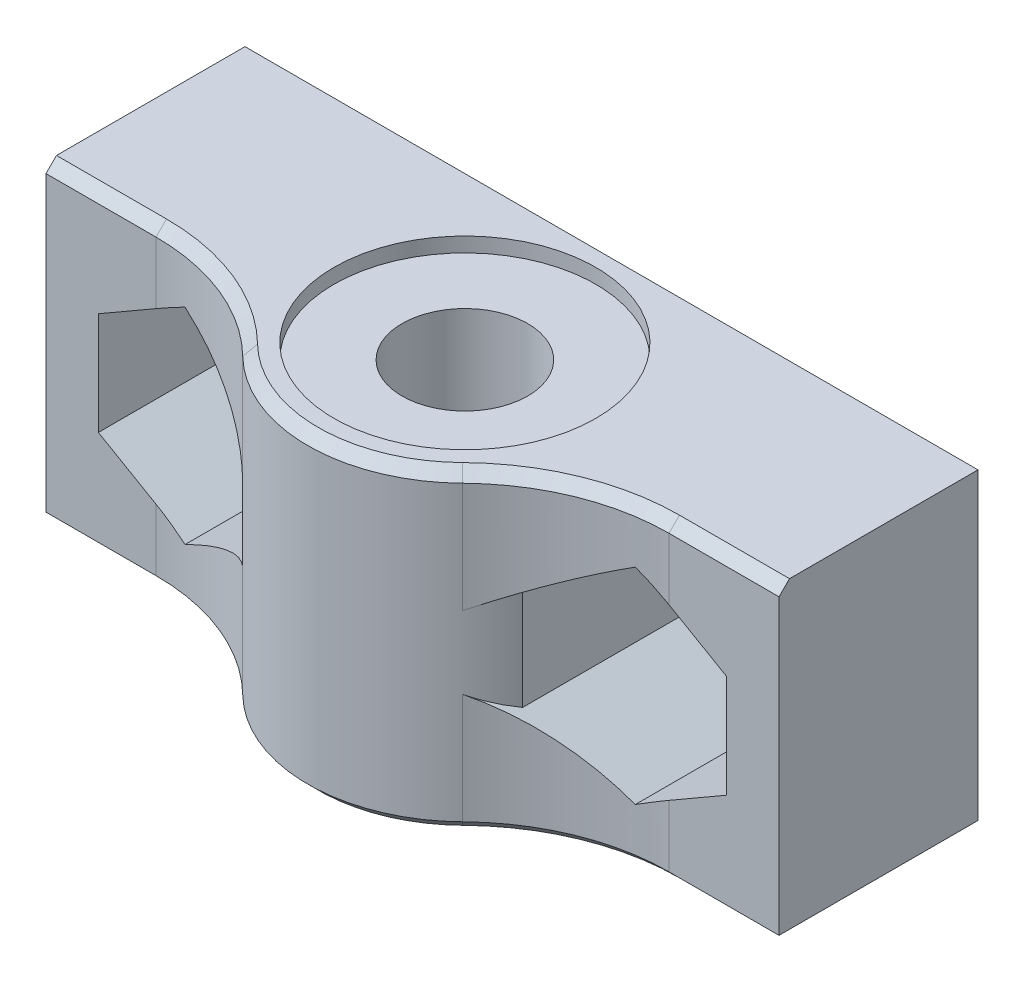
SolidWorks part; units mm, degrees
note: The reader was unsure of these and kept them because the rebuilt part matched: shared geometry of "Sketch6<3>".
ref_plane "Front Plane" through (0, 0, 0) normal (0, 0, 1) x (1, 0, 0)
ref_plane "Top Plane" through (0, 0, 0) normal (0, 1, 0) x (1, 0, 0)
ref_plane "Right Plane" through (0, 0, 0) normal (1, 0, 0) x (0, 0, -1)
sketch "Sketch1" plane through (0, 0, 0) normal (0, 0, 1) x (1, 0, 0)
  line L1 (-17.5, 0) -> (17.5, 0)
  line L2 (-17.5, 0) -> (-17.5, -15)
  line L3 (-17.5, -15) -> (17.5, -15)
  line L4 (17.5, 0) -> (17.5, -15)
  point P4 (0, 0)
  dimension "D1" = 35
  dimension "D2" = 15
extrude "Boss-Extrude1" add sketch "Sketch1" along normal blind 10
sketch "Sketch3" plane through (0, 0, 0) normal (0, 1, 0) x (1, 0, 0)
  line L0 (17.5, 0) -> (-17.5, 0) construction
  line L1 (0, -10) -> (0, -7.5) construction
  line L3 (17.5, -10) -> (-17.5, -10) construction
  circle A0 centre (0, -7.5) radius 7.5
  dimension "D1" = 15
extrude "Boss-Extrude2" add sketch "Sketch3" against normal through all
sketch "Sketch2" plane through (0, 0, 10) normal (0, 0, 1) x (1, 0, 0)
  line L0 (-17.5, -7.5) -> (-10.75, -7.5) construction
  line L1 (-10.75, -12.4075) -> (-6.5, -9.9537)
  line L2 (-6.5, -9.9537) -> (-6.5, -5.0463)
  line L3 (-6.5, -5.0463) -> (-10.75, -2.5925)
  line L4 (-10.75, -2.5925) -> (-15, -5.0463)
  line L5 (-15, -5.0463) -> (-15, -9.9537)
  line L6 (-15, -9.9537) -> (-10.75, -12.4075)
  line L7 (-17.5, 0) -> (-17.5, -15) construction
  line L8 (-10.75, -2.5925) -> (-10.75, -7.5) construction
  circle A0 centre (-10.75, -7.5) radius 4.25 construction
  dimension "D1" = 8.5
  dimension "D2" = 2.5
extrude "Cut-Extrude1" cut sketch "Sketch2" against normal blind 7.5 and the other way blind 10
sketch "Sketch5" plane through (0, 0, 2.5) normal (0, 0, 1) x (1, 0, 0)
  line L0 (-10.75, -2.5925) -> (-10.75, -12.4075) construction
  circle A0 centre (-10.75, -7.5) radius 2.75
  dimension "D1" = 5.5
extrude "Cut-Extrude3" cut sketch "Sketch5" against normal through all
mirror "Mirror1" about plane through (0, 0, 0) normal (1, 0, 0) of "Cut-Extrude3", "Cut-Extrude1"
sketch "Sketch4" plane through (0, 0, 0) normal (0, 1, 0) x (1, 0, 0)
  circle A0 centre (0, -7.5) radius 3
  arc A1 (-7.0711, -10) -> (7.0711, -10) centre (0, -7.5) ccw construction
  dimension "D1" = 6
extrude "Cut-Extrude2" cut sketch "Sketch4" against normal through all
fillet "Fillet1" radius 10 4 edges at (7.0711, -2.3583, 10) (-7.0711, -2.3583, 10) (-7.0711, -12.6417, 10) (7.0711, -12.6417, 10)
sketch "Sketch6" plane through (0, -15, 0) normal (0, -1, 0) x (1, 0, 0)
  circle A0 centre (0, 7.5) radius 6.25
  dimension "D1" = 12.5
extrude "Cut-Extrude4" cut sketch "Sketch6" against normal blind 0.7 contours A0
extrude "Cut-Extrude5" cut sketch "Sketch6<3>" along normal blind 0.7 from surface at -15 starting at face at (-3, 0, 7.5)
sketch "Sketch6<3>" plane through (0, -15, 0) normal (0, -1, 0) x (1, 0, 0) same geometry as "Sketch6"
chamfer "Chamfer1" distance 0.5 angle 45 18 edges at (8, -7.5, 0) (-8, -7.5, 0) (0, 0, 0) (-17.5, -7.5, 0) (0, -15, 0) (17.5, -7.5, 0) (17.5, -15, 5) (-17.5, -15, 5) (-14.8737, -15, 10) (14.8737, -15, 10) (-8.4678, -15, 10.7418) (8.4678, -15, 10.7418) (0, -15, 15) (-14.8737, 0, 10) (14.8737, 0, 10) (-8.4678, 0, 10.7418) (8.4678, 0, 10.7418) (0, 0, 15)
